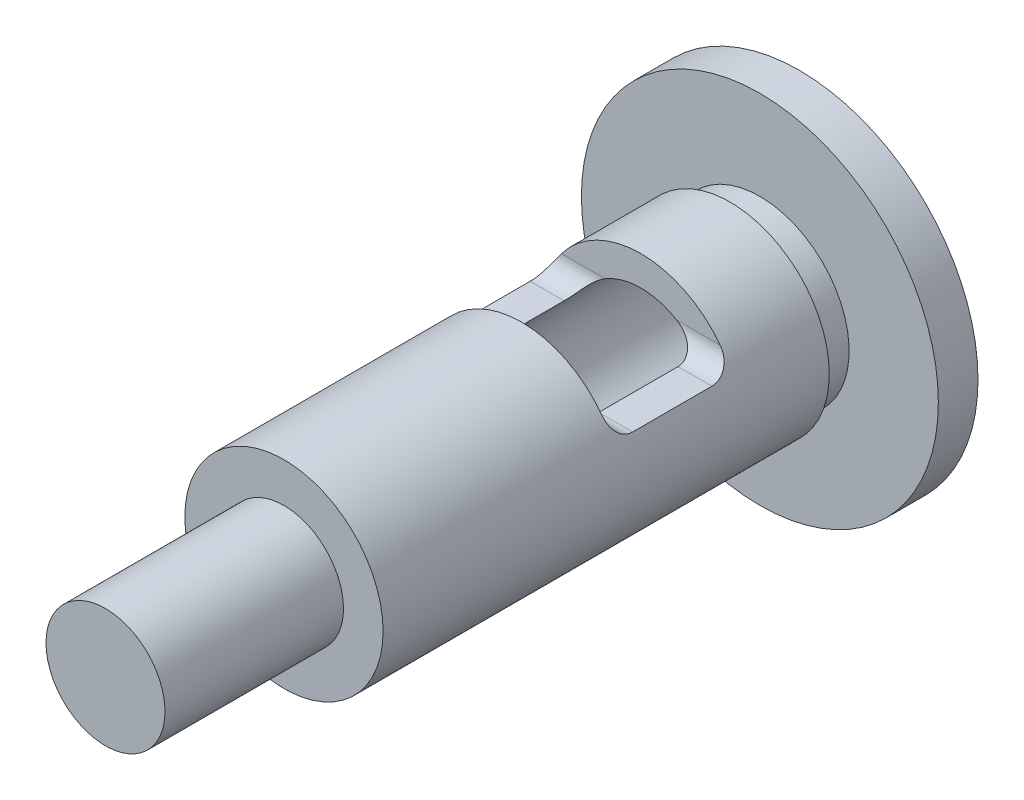
SolidWorks part; units mm, degrees
ref_plane "Plan de face" through (0, 0, 0) normal (0, 0, 1) x (1, 0, 0)
ref_plane "Plan de dessus" through (0, 0, 0) normal (0, 1, 0) x (1, 0, 0)
ref_plane "Plan de droite" through (0, 0, 0) normal (1, 0, 0) x (0, 0, -1)
sketch "Esquisse1" plane through (0, 0, 0) normal (1, 0, 0) x (0, 0, -1)
  line L0 (0, 0) -> (-70, 0) construction
  line L1 (0, 0) -> (0, 18) construction
  line L2 (-70, 0) -> (-36, 0)
  line L3 (-70, 0) -> (-70, 6)
  line L4 (-70, 6) -> (-52, 6)
  line L5 (-52, 6) -> (-52, 10)
  line L6 (-52, 10) -> (-7, 10)
  line L7 (-7, 10) -> (-7, 9)
  line L8 (-7, 9) -> (-4, 9)
  line L9 (0, 18) -> (-4, 18)
  line L10 (-4, 18) -> (-4, 9)
  line L11 (0, 18) -> (0, 7)
  line L12 (0, 7) -> (-32, 7)
  line L13 (-36, 0) -> (-32, 7)
  dimension "D1" = 70
  dimension "D2" = 18
  dimension "D3" = 34
  dimension "D4" = 6
  dimension "D5" = 18
  dimension "D6" = 10
  dimension "D7" = 1
  dimension "D8" = 3
  dimension "D9" = 4
  dimension "D10" = 7
  dimension "D11" = 4
revolve "Révolution1" add sketch "Esquisse1" angle 360 about L0
sketch "Esquisse2" plane through (0, 0, 0) normal (1, 0, 0) x (0, 0, -1)
  line L0 (-7, 10) -> (-16, 10) construction
  line L1 (-16, 10) -> (-28, 10)
  line L2 (-28, 10) -> (-28, 6)
  line L3 (-26, 4) -> (-18, 4)
  line L4 (-16, 6) -> (-16, 10)
  arc A0 (-26, 4) -> (-28, 6) centre (-26, 6) cw
  arc A1 (-16, 6) -> (-18, 4) centre (-18, 6) cw
  point P8 (-28, 4)
  dimension "D4" = 2
  dimension "D5" = 2
  dimension "D1" = 9
  dimension "D2" = 12
  dimension "D3" = 6
extrude "Enlèv. mat.-Extru.1" cut sketch "Esquisse2" against normal blind 10 and the other way blind 10
sketch "Esquisse3" plane through (0, 0, 0) normal (0, 0, -1) x (-1, 0, 0)
  line L0 (0, 0) -> (-12, 0) construction
  line L1 (-12, 0) -> (-18, 0)
  line L2 (0, 0) -> (0, 22.2707) construction
  line L3 (-12, 0) -> (-7, 16.5831)
  line L4 (12, 0) -> (18, 0)
  line L5 (12, 0) -> (7, 16.5831)
  circle A0 centre (0, 0) radius 18 construction
  arc A1 (-18, 0) -> (18, 0) centre (0, 0) ccw
  arc A2 (7, 16.5831) -> (-7, 16.5831) centre (0, 0) ccw
  dimension "D1" = 12
  dimension "D2" = 7
